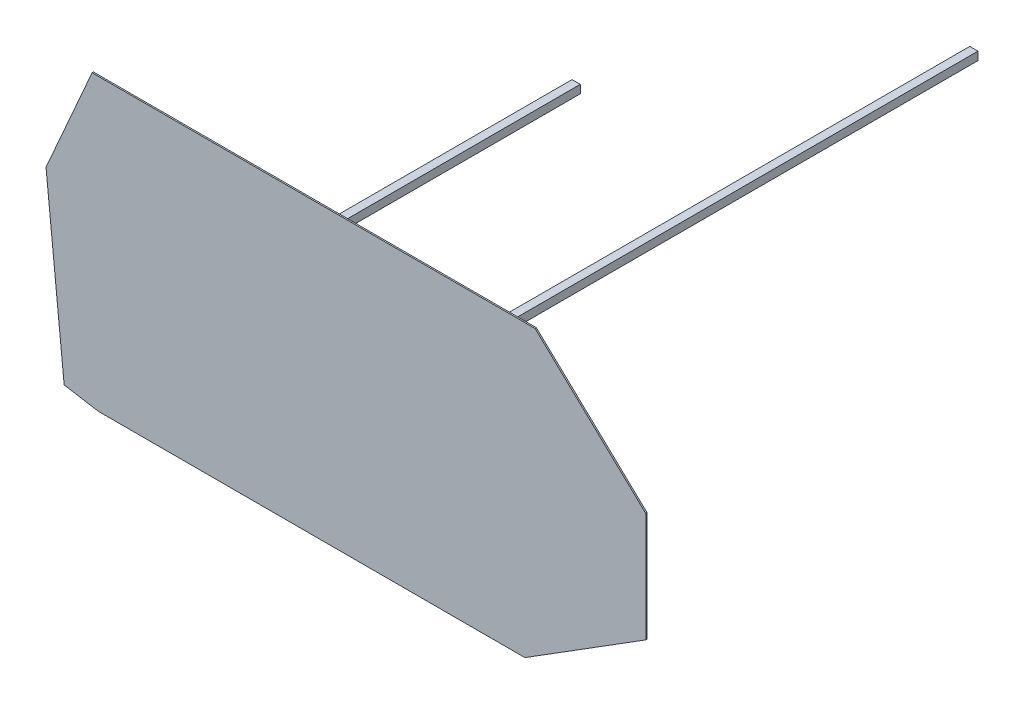
SolidWorks part; units mm, degrees
ref_plane "Front" through (0, 0, 0) normal (0, 0, 1) x (1, 0, 0)
ref_plane "Top" through (0, 0, 0) normal (0, 1, 0) x (1, 0, 0)
ref_plane "Right" through (0, 0, 0) normal (1, 0, 0) x (0, 0, -1)
sketch "Esquisse1" plane through (0, 0, 0) normal (0, 0, 1) x (1, 0, 0)
  line L1 (0, 0) -> (50, 0)
  line L2 (0, 0) -> (0, 50)
  line L3 (0, 50) -> (50, 50)
  line L4 (50, 0) -> (50, 50)
  dimension "D1" = 50
  dimension "D2" = 50
extrude "Boss.-Extru.1" add sketch "Esquisse1" along normal blind 5
sketch "Esquisse2" plane through (0, 0, 5) normal (0, 0, 1) x (1, 0, 0)
  line L0 (-5.6535, 9.3332) -> (57.2852, 53.4636)
  line L1 (57.2852, 53.4636) -> (231.6916, 53.4636)
  line L2 (231.6916, 53.4636) -> (285.9358, -3.0527)
  line L3 (285.9358, -3.0527) -> (284, -82.5096)
  line L4 (284, -82.5096) -> (207.7062, -129.7611)
  line L5 (207.7062, -129.7611) -> (50.4315, -129.7611)
  line L6 (50.4315, -129.7611) -> (-5.6535, -85.3866)
  line L7 (-5.6535, -85.3866) -> (-5.6535, 9.3332)
  line L8 (261, -129.7611) -> (23, -129.7611) construction
  line L9 (284, 24.7389) -> (284, -104.2611) construction
extrude "Boss.-Extru.2" add sketch "Esquisse2" against normal up to vertex (5 mm away) up to point (0, 50, 0)
sketch "Esquisse3" plane through (0, 0, 0) normal (0, 0, -1) x (-1, 0, 0)
  line L0 (0, -121.7217) -> (6, -121.7217)
  line L1 (6, -121.7217) -> (6, -115.7217)
  line L2 (6, -115.7217) -> (0, -115.7217)
  line L4 (0, -115.7217) -> (0, -121.7217)
  line L6 (-284, 44.2389) -> (-290, 44.2389)
  line L7 (-284, 44.2389) -> (-284, 50.2389)
  line L8 (-284, 50.2389) -> (-290, 50.2389)
  line L9 (-290, 44.2389) -> (-290, 50.2389)
  dimension "D1" = 6
  dimension "D2" = 6
  dimension "D3" = 6
  dimension "D4" = 6
extrude "Boss.-Extru.3" add sketch "Esquisse3" along normal blind 350
sketch "Esquisse4" plane through (0, 0, 5) normal (0, 0, 1) x (1, 0, 0)
  line L0 (0, 69.5906) -> (322.9861, 69.5906)
  line L1 (322.9861, 69.5906) -> (403.7416, -6.8693)
  line L2 (403.7416, -6.8693) -> (403.7416, -86.7162)
  line L3 (403.7416, -86.7162) -> (315.5911, -141.9628)
  line L4 (315.5911, -141.9628) -> (4.7577, -141.9628)
  line L5 (4.7577, -141.9628) -> (-20.3705, -137.7747)
  line L6 (-20.3705, -137.7747) -> (-33.6198, -6.8693)
  line L7 (-33.6198, -6.8693) -> (0, 69.5906)
extrude "Boss.-Extru.4" add sketch "Esquisse4" along normal blind 1
